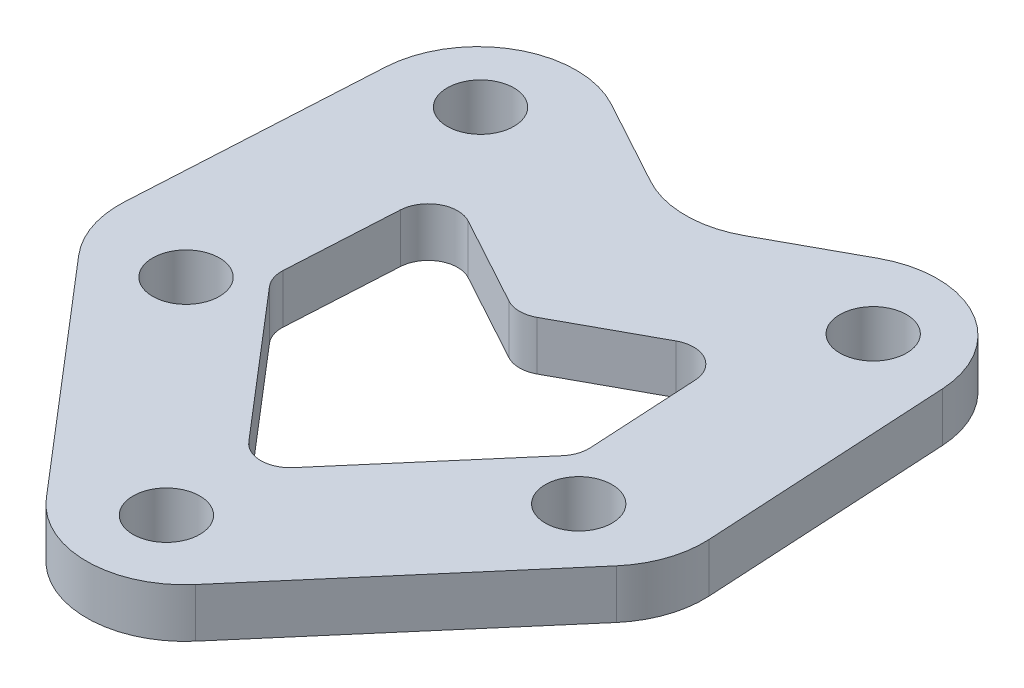
SolidWorks part; units mm, degrees
ref_plane "Front Plane" through (0, 0, 0) normal (0, 0, 1) x (1, 0, 0)
ref_plane "Top Plane" through (0, 0, 0) normal (0, 1, 0) x (1, 0, 0)
ref_plane "Right Plane" through (0, 0, 0) normal (1, 0, 0) x (0, 0, -1)
sketch "Sketch1" plane through (0, 0, 0) normal (0, 1, 0) x (1, 0, 0)
  line L0 (-17.4625, 31.75) -> (0, 22.225)
  line L1 (0, 22.225) -> (17.4625, 31.75)
  line L2 (17.4625, 31.75) -> (19.05, 3.175)
  line L3 (19.05, 3.175) -> (0, -19.05)
  line L4 (0, -19.05) -> (-19.05, 3.175)
  line L5 (-19.05, 3.175) -> (-17.4625, 31.75)
  point P2 (0, 12.7317)
  point P7 (-23.3107, 15.4952)
  point P8 (22.6738, 14.3313)
  point P9 (21.8925, 14.2196)
  point P10 (0, 0)
  point P12 (0, 0)
  point P13 (0, -26.1507)
  point P14 (-16.6631, -3.6496)
  point P15 (22.071, 16.28)
  point P16 (19.0173, 21.9849)
  point P17 (-16.3416, -6.3293)
  point P18 (0, -20.8469)
  point P19 (-12.7, -4.3998)
  point P20 (0, 0)
  point P21 (0, 12.7)
  point P22 (19.05, 23.8254)
  point P23 (19.05, 22.8517)
  point P24 (0, 21.7965)
  point P25 (-12.7, -3.175)
  point P26 (0, 21.8976)
  point P27 (15.875, 3.4925)
  dimension "D1" = 34.925
  dimension "D2" = 22.225
  dimension "D3" = 19.05
  dimension "D4" = 19.05
  dimension "D5" = 3.175
  dimension "D6" = 9.525
extrude "Boss-Extrude1" add sketch "Sketch1" along normal blind 3.175
sketch "Sketch2" plane through (0, 3.175, 0) normal (0, 1, 0) x (1, 0, 0)
  circle A0 centre (0, -10.4775) radius 2.159
  circle A1 centre (-12.7, 3.4925) radius 2.159
  circle A2 centre (12.7, 3.4925) radius 2.159
  circle A3 centre (-12.7, 22.5425) radius 2.159
  circle A4 centre (12.7, 22.5425) radius 2.159
  circle A5 centre (-12.7, 3.4925) radius 7.239 construction
  point P15 (-13.2536, 22.5425)
  point P16 (0, 0)
  point P17 (0, 0)
  point P18 (13.0554, 2.9235)
  dimension "D1" = 4.318
  dimension "D3" = 25.4
  dimension "D2" = 10.4775
  dimension "D4" = 19.05
extrude "Cut-Extrude1" cut sketch "Sketch2" against normal through all
sketch "Sketch3" plane through (0, 3.175, 0) normal (0, 1, 0) x (1, 0, 0)
  line L27 (-9.3667, 17.2076) -> (-9.9755, 6.2484)
  line L28 (-9.9755, 6.2484) -> (0, -5.3897)
  line L29 (0, -5.3897) -> (9.9755, 6.2484)
  line L30 (9.9755, 6.2484) -> (9.3667, 17.2076)
  line L31 (9.3667, 17.2076) -> (0, 12.0985)
  line L32 (0, 12.0985) -> (-9.3667, 17.2076)
  line L33 (-9.3667, 17.2076) -> (-9.9755, 6.2484)
  line L34 (-9.9755, 6.2484) -> (0, -5.3897)
  line L35 (0, -5.3897) -> (9.9755, 6.2484)
  line L36 (9.9755, 6.2484) -> (9.3667, 17.2076)
  line L37 (9.3667, 17.2076) -> (0, 12.0985)
  line L38 (0, 12.0985) -> (-9.3667, 17.2076)
  dimension "D1" = 8.89
extrude "Cut-Extrude2" cut sketch "Sketch3" against normal through all
fillet "Fillet1" radius 6.35 6 edges at (-19.05, 1.5875, -3.175) (0, 1.5875, 19.05) (19.05, 1.5875, -3.175) (17.4625, 1.5875, -31.75) (-17.4625, 1.5875, -31.75) (0, 1.5875, -22.225)
fillet "Fillet2" radius 1.905 6 edges at (-9.9755, 1.5875, -6.2484) (-9.3667, 1.5875, -17.2076) (0, 1.5875, -12.0985) (9.3667, 1.5875, -17.2076) (9.9755, 1.5875, -6.2484) (0, 1.5875, 5.3897)
